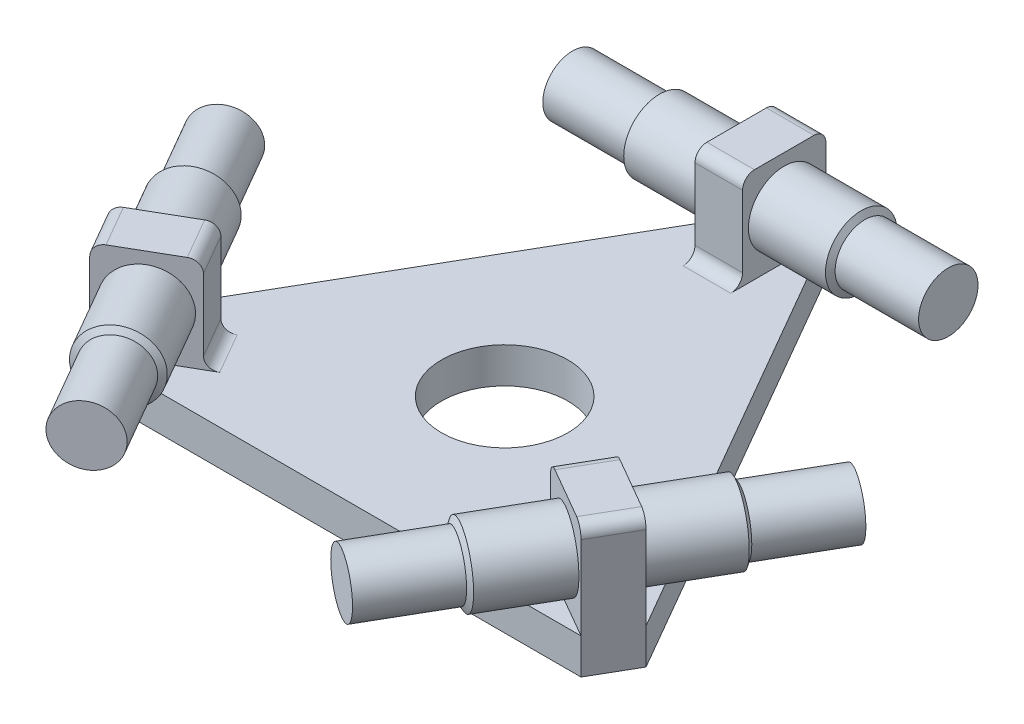
SolidWorks part; units mm, degrees
ref_plane "Front Plane" through (0, 0, 0) normal (0, 0, 1) x (1, 0, 0)
ref_plane "Top Plane" through (0, 0, 0) normal (0, 1, 0) x (1, 0, 0)
ref_plane "Right Plane" through (0, 0, 0) normal (1, 0, 0) x (0, 0, -1)
sketch "Sketch1" plane through (0, 0, 0) normal (0, 1, 0) x (1, 0, 0)
  line L0 (2.54, 31.75) -> (-2.54, 31.75)
  line L1 (27.4963, -15.875) -> (0, 31.75) construction
  line L2 (0, 31.75) -> (-27.4963, -15.875) construction
  line L3 (-27.4963, -15.875) -> (27.4963, -15.875) construction
  line L4 (-26.2263, -18.0747) -> (-28.7663, -13.6753)
  line L5 (26.2263, -18.0747) -> (28.7663, -13.6753)
  line L6 (-2.54, 31.75) -> (-28.7663, -13.6753)
  line L7 (-26.2263, -18.0747) -> (26.2263, -18.0747)
  line L8 (2.54, 31.75) -> (28.7663, -13.6753)
  line L9 (0, 31.75) -> (0, -18.0747) construction
  line L10 (-27.4963, -15.875) -> (15.6532, 9.0374) construction
  line L11 (27.4963, -15.875) -> (-15.6532, 9.0374) construction
  circle A1 centre (0, 0) radius 31.75 construction
  point P12 (0, 31.75)
  point P13 (-27.4963, -15.875)
  point P16 (27.4963, -15.875)
  dimension "D1" = 63.5
  dimension "D2" = 5.08
  dimension "D3" = 5.08
  dimension "D4" = 5.08
extrude "Boss-Extrude1" add sketch "Sketch1" along normal blind 3.81
hole_wizard "17/32 (0.53125) Diameter Hole1" positions "3DSketch2" profile "Sketch4" hole size "17/32" standard "ANSI Inch" end condition through all
sketch3d "3DSketch2"
  point P0 (0, 3.81, 0)
sketch "Sketch4" plane through (0, 3.81, 0) normal (1, 0, 0) x (0, 0, 1)
  line L0 (0, 0) -> (0, 3.81)
  line L1 (0, 3.81) -> (6.7469, 3.81)
  line L2 (6.7469, 3.81) -> (6.7469, 0)
  line L5 (6.7469, 0) -> (0, 0)
  line L11 (0, -6.35) -> (0, 107.95) construction
  dimension "Thru Hole Dia." = 13.4937
  dimension "Thru Hole Depth" = 3.81
sketch "Sketch5" plane through (0, 3.81, 0) normal (0, 1, 0) x (1, 0, 0)
  line L4 (-28.7663, -13.6753) -> (-26.2263, -18.0747) construction
  line L15 (-28.7663, -13.6753) -> (-26.2263, -18.0747)
  line L22 (-18.5273, -13.6297) -> (-21.0673, -9.2303)
  line L23 (-26.2263, -18.0747) -> (-18.5273, -13.6297)
  line L24 (-21.0673, -9.2303) -> (-28.7663, -13.6753)
  point P1 (-27.4963, -15.875)
  point P2 (-27.4963, -15.875)
  dimension "D1" = 5.08
  dimension "D2" = 8.89
extrude "Boss-Extrude2" add sketch "Sketch5" along normal blind 10.16
pattern_circular "CirPattern19" count 3 over 360 about axis through (0, 0, 0) along (0, 1, 0) of "Boss-Extrude2"
sketch "Sketch6" plane through (1.27, 0, 2.1997) normal (0.5, 0, 0.866) x (0.866, 0, -0.5)
  line L0 (-27.305, 13.97) -> (-27.305, 3.81) construction
  line L3 (-31.75, 13.97) -> (-22.86, 13.97) construction
  line L4 (-31.75, 3.81) -> (-22.86, 3.81) construction
  circle A0 centre (-27.305, 8.89) radius 3.825
  dimension "D1" = 7.65
extrude "Boss-Extrude3" add sketch "Sketch6" along normal blind 8.63 and the other way offset from surface (13.71 mm away) 8.63 other way up to face at (-24.9168, 8.89, 11.4528)
sketch "Sketch7" plane through (5.585, 0, 9.6735) normal (0.5, 0, 0.866) x (0.866, 0, -0.5)
  circle A0 centre (-27.305, 8.89) radius 3.175
  dimension "D1" = 6.35
extrude "Boss-Extrude4" add sketch "Sketch7" along normal blind 8.89 and the other way offset from surface (31.23 mm away) 8.89 other way up to face at (-25.9193, 8.89, 2.0665)
pattern_circular "CirPattern21" count 3 over 360 about axis through (0, 0, 0) along (0, 1, 0) of "Boss-Extrude3"
pattern_circular "CirPattern28" count 3 over 360 about axis through (0, 0, 0) along (0, 1, 0) of "Boss-Extrude4"
chamfer "Chamfer3" distance 0.4 angle 60 6 edges at (-14.7493, 8.89, 21.4135) (-11.17, 8.89, -23.48) (11.17, 8.89, -23.48) (25.9193, 8.89, 2.0665) (14.7493, 8.89, 21.4135) (-25.9193, 8.89, 2.0665)
fillet "Fillet4" radius 1.27 9 edges at (-19.7973, 3.81, 11.43) (-27.4963, 13.97, 15.875) (-19.7973, 13.97, 11.43) (19.7973, 3.81, 11.43) (27.4963, 13.97, 15.875) (19.7973, 13.97, 11.43) (0, 3.81, -22.86) (0, 13.97, -31.75) (0, 13.97, -22.86)
sketch "Sketch8" plane through (0, 3.81, 0) normal (0, 1, 0) x (1, 0, 0)
  line L0 (-10.77, 23.48) -> (-10.77, 15.86)
  line L1 (-10.77, 15.86) -> (-11.7141, 15.86)
  line L2 (-2.54, 31.75) -> (-28.7663, -13.6753) construction
  line L3 (10.77, 23.48) -> (10.77, 15.86)
  line L4 (10.77, 15.86) -> (11.7141, 15.86)
  line L5 (28.7663, -13.6753) -> (2.54, 31.75) construction
  line L6 (37.8221, 19.2861) -> (32.6392, 22.2784)
  line L7 (37.8221, 19.2861) -> (31.223, 23.0961)
  line L8 (31.223, 23.0961) -> (31.6951, 23.9137)
  line L9 (27.0521, 0.6319) -> (21.8692, 3.6243)
  line L10 (27.0521, 0.6319) -> (20.453, 4.4419)
  line L11 (20.453, 4.4419) -> (19.981, 3.6243)
  line L12 (9.894, -20.699) -> (15.077, -17.7066)
  line L13 (9.894, -20.699) -> (16.4931, -16.889)
  line L14 (-10.77, 23.48) -> (-10.77, 17.4952)
  line L15 (10.77, 23.48) -> (10.77, 17.4952)
  line L16 (16.4931, -16.889) -> (16.9652, -17.7066)
  line L17 (-0.876, -2.0448) -> (4.307, 0.9476)
  line L18 (-0.876, -2.0448) -> (5.7231, 1.7652)
  line L19 (5.7231, 1.7652) -> (5.2511, 2.5828)
  line L20 (-10.77, 17.4952) -> (-11.7141, 15.86)
  line L21 (4.307, 0.9476) -> (5.2511, 2.5828)
  line L22 (15.077, -17.7066) -> (16.9652, -17.7066)
  line L23 (21.8692, 3.6243) -> (19.981, 3.6243)
  line L24 (31.6951, 23.9137) -> (32.6392, 22.2784)
  line L25 (10.77, 17.4952) -> (11.7141, 15.86)
  dimension "D1" = 7.62
  dimension "D2" = 7.62
  dimension "D4" = 33.2453
  dimension "D5" = 21.6953
  dimension "D3" = 3
extrude "Cut-Extrude2" [suppressed] cut sketch "Sketch8" against normal through all
ref_plane "Plane1" through (0, 13.97, 0) normal (0, 1, 0) x (1, 0, 0)
